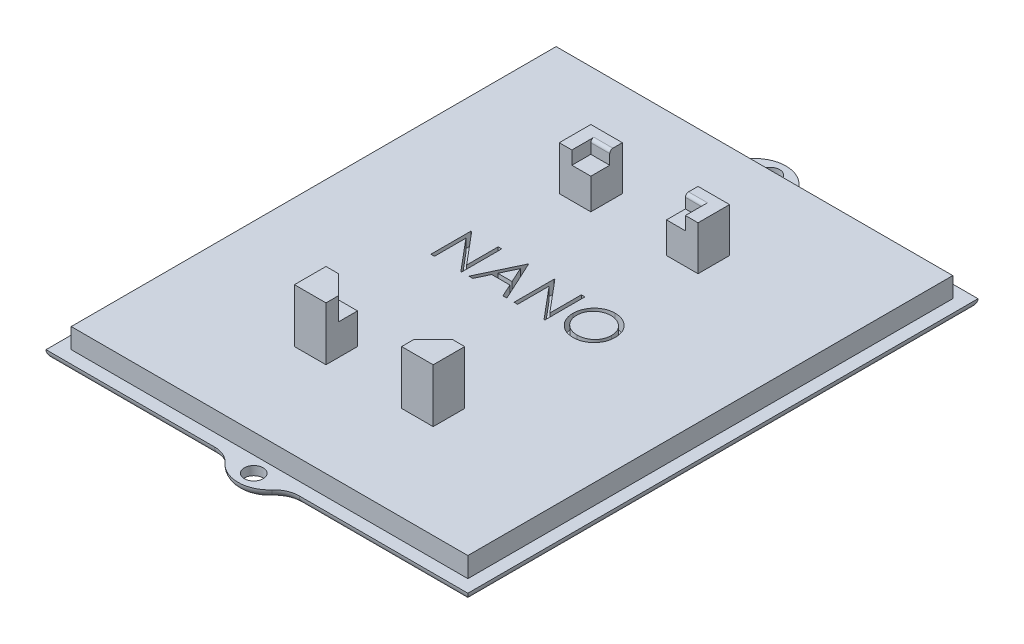
SolidWorks part; units mm, degrees
ref_plane "Front Plane" through (0, 0, 0) normal (0, 0, 1) x (1, 0, 0)
ref_plane "Top Plane" through (0, 0, 0) normal (0, 1, 0) x (1, 0, 0)
ref_plane "Right Plane" through (0, 0, 0) normal (1, 0, 0) x (0, 0, -1)
sketch "Sketch1" plane through (0, 0, 0) normal (0, 1, 0) x (1, 0, 0)
  line L0 (-31.45, 38.45) -> (31.45, 38.45)
  line L5 (-31.45, 38.45) -> (-31.45, -38.45)
  line L6 (-31.45, -38.45) -> (31.45, -38.45)
  line L7 (31.45, 38.45) -> (31.45, -38.45)
  point P11 (-31.45, 0)
  point P12 (0, -38.45)
  dimension "D3" = 76.9
  dimension "D4" = 62.9
extrude "Boss-Extrude1" add sketch "Sketch1" along normal blind 4.575
sketch "Sketch6" plane through (0, 0, 0) normal (0, -1, 0) x (1, 0, 0)
  line L8 (-33.45, 40.45) -> (-33.45, -40.45)
  line L9 (-33.45, -40.45) -> (33.45, -40.45)
  line L10 (33.45, -40.45) -> (33.45, 40.45)
  line L11 (33.45, 40.45) -> (-33.45, 40.45)
  line L12 (-33.45, 40.45) -> (-33.45, -40.45)
  line L13 (-33.45, -40.45) -> (33.45, -40.45)
  line L14 (33.45, -40.45) -> (33.45, 40.45)
  line L15 (33.45, 40.45) -> (-33.45, 40.45)
  dimension "D1" = 2
extrude "Boss-Extrude4" add sketch "Sketch6" against normal blind 1.4
sketch "Sketch4" plane through (0, 0, 0) normal (0, 1, 0) x (1, 0, 0)
  line L3 (33.45, -40.45) -> (-33.45, -40.45) construction
  line L4 (-31.45, -38.45) -> (31.45, -38.45) construction
  line L5 (6.7082, -40.45) -> (-6.7082, -40.45)
  arc A3 (-6.7082, -40.45) -> (-3.7268, -41.7833) centre (-6.7082, -44.45) cw
  arc A4 (-3.7268, -41.7833) -> (3.7268, -41.7833) centre (0, -38.45) ccw
  arc A5 (3.7268, -41.7833) -> (6.7082, -40.45) centre (6.7082, -44.45) cw
  dimension "D1" = 5
  dimension "D2" = 4
extrude "Boss-Extrude3" add sketch "Sketch4" along normal blind 1.4
sketch "Sketch7" plane through (0, 1.4, 0) normal (0, 1, 0) x (1, 0, 0)
  line L0 (0, -38.45) -> (0, -43.45) construction
  line L1 (-31.45, -38.45) -> (31.45, -38.45) construction
  arc A0 (-3.7268, -41.7833) -> (3.7268, -41.7833) centre (0, -38.45) ccw construction
  circle A1 centre (0, -40.95) radius 1.5
  dimension "D1" = 3
extrude "Cut-Extrude2" cut sketch "Sketch7" against normal up to next
mirror "Mirror1" about plane through (0, 0, 0) normal (0, 0, 1) of "Cut-Extrude2", "Boss-Extrude3"
fillet "Fillet1" radius 1.4 12 edges at (33.45, 0, 0) (20.0791, 0, -40.45) (5.0752, 0, -40.7985) (0, 0, -43.45) (-5.0752, 0, -40.7985) (-20.0791, 0, -40.45) (-33.45, 0, 0) (-20.0791, 0, 40.45) (-5.0752, 0, 40.7985) (0, 0, 43.45) (5.0752, 0, 40.7985) (20.0791, 0, 40.45)
sketch "Sketch2" plane through (0, 4.575, 0) normal (0, 1, 0) x (1, 0, 0)
  line L1 (-11, -23.5) -> (-6, -23.5)
  line L2 (-11, -23.5) -> (-11, -18.5)
  line L3 (-11, -18.5) -> (-6, -18.5)
  line L4 (-6, -23.5) -> (-6, -18.5)
  line L5 (11, -23.5) -> (6, -23.5)
  line L6 (11, -23.5) -> (11, -18.5)
  line L7 (11, -18.5) -> (6, -18.5)
  line L8 (6, -23.5) -> (6, -18.5)
  line L9 (-6, 23.5) -> (-11, 23.5)
  line L10 (-6, 23.5) -> (-6, 18.5)
  line L11 (-6, 18.5) -> (-11, 18.5)
  line L12 (-11, 23.5) -> (-11, 18.5)
  line L13 (6, 23.5) -> (11, 23.5)
  line L14 (6, 23.5) -> (6, 18.5)
  line L15 (6, 18.5) -> (11, 18.5)
  line L16 (11, 23.5) -> (11, 18.5)
  line L17 (-6, -18.5) -> (6, -18.5) construction
  line L18 (-6, -18.5) -> (-6, 18.5) construction
  line L19 (-6, 18.5) -> (6, 18.5) construction
  line L20 (6, -18.5) -> (6, 18.5) construction
  point P17 (-6, 0)
  point P18 (0, 18.5)
  point P19 (-13.6874, 18.5)
  dimension "D1" = 37
  dimension "D4" = 12
  dimension "D2" = 47
  dimension "D3" = 22
extrude "Boss-Extrude2" add sketch "Sketch2" along normal blind 7
sketch "Sketch5" plane through (0, 4.575, 0) normal (0, 1, 0) x (1, 0, 0)
  line L0 (-15, 0) -> (15, 0) construction
  text T0 "NANO\r\n" font "Century Gothic" height in points 24
  point P6 (0, 0)
  dimension "D1" = 30
extrude "Letters" cut sketch "Sketch5" against normal blind 2
sketch "Sketch8" plane through (0, 11.575, 0) normal (0, 1, 0) x (1, 0, 0)
  line L1 (-9, 21.5) -> (9, 21.5)
  line L2 (-9, 21.5) -> (-9, -21.5)
  line L3 (-9, -21.5) -> (9, -21.5)
  line L4 (9, 21.5) -> (9, -21.5)
  point P4 (0, 21.5)
  point P6 (-9, 0)
  dimension "D1" = 18
  dimension "D2" = 43
extrude "Cut-Extrude3" cut sketch "Sketch8" against normal blind 2.1
sketch "Sketch10" plane through (0, 11.575, 0) normal (0, 1, 0) x (1, 0, 0)
  line L0 (-11, -18.5) -> (-11, -23.5)
  line L1 (-11, -23.5) -> (-6, -23.5)
  line L2 (-6, -23.5) -> (-6, -21.5)
  line L3 (-6, -21.5) -> (-9, -18.5)
  line L4 (-9, -18.5) -> (-11, -18.5)
  line L5 (6, -21.5) -> (6, -23.5)
  line L6 (6, -23.5) -> (11, -23.5)
  line L7 (11, -23.5) -> (11, -18.5)
  line L8 (11, -18.5) -> (9, -18.5)
  line L9 (9, -18.5) -> (6, -21.5)
extrude "Boss-Extrude5" add sketch "Sketch10" along normal blind 1.5
fillet "Fillet2" radius 0.5 2 edges at (7.5, 11.575, 20) (-7.5, 11.575, 20)
fillet "Fillet3" radius 0.5 2 edges at (7.5, 11.575, -21.5) (-7.5, 11.575, -21.5)
